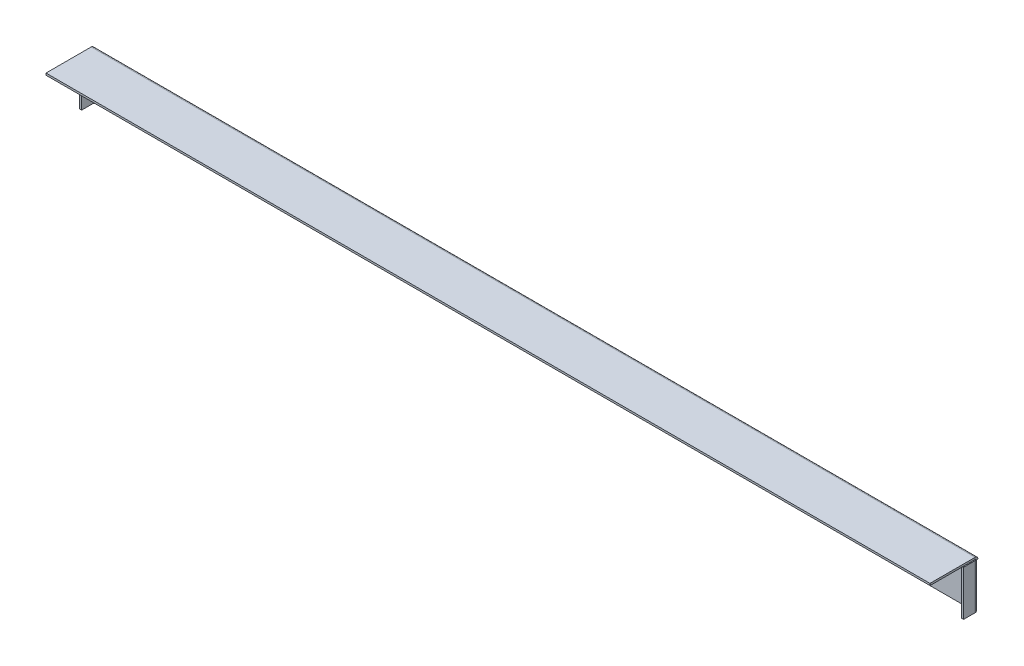
SolidWorks part; units mm, degrees
note: The reader was unsure of these and kept them because the rebuilt part matched: flange length of "Edge-Flange1", "Edge-Flange2".
ref_plane "Front Plane" through (0, 0, 0) normal (0, 0, 1) x (1, 0, 0)
ref_plane "Top Plane" through (0, 0, 0) normal (0, 1, 0) x (1, 0, 0)
ref_plane "Right Plane" through (0, 0, 0) normal (1, 0, 0) x (0, 0, -1)
sketch "BaseFlange" plane through (0, 0, 0) normal (0, 0, 1) x (1, 0, 0)
  line L1 (460, 0) -> (-460, 0)
  line L2 (460, 0) -> (460, -50)
  line L3 (460, -50) -> (-460, -50)
  line L4 (-460, 0) -> (-460, -50)
  line L5 (460, 0) -> (-460, -50) construction
  line L6 (460, -50) -> (-460, 0) construction
  point P0 (0, -25)
  dimension "BoxWidth" = 920
  dimension "D2" = 50
base flange "Base-Flange1" sketch "BaseFlange" thickness 2 reverse thickness direction yes parameters "D1"=1
edge flange "Edge-Flange1" sketch "Sketch8" flange angle 90 flange length 50 flange position material inside bend radius 1 thickness 2 parameters "D6"=10
sketch "Sketch8" plane through (0, 0, 2) normal (0, -1, 0) x (1, 0, 0)
  line L1 (-460, 0) -> (460, 0) construction
  line L2 (460, 0) -> (460, 48)
  line L3 (460, 48) -> (-460, 48)
  line L4 (-460, 48) -> (-460, 0)
  line L5 (-460, 0) -> (460, 0)
bend "EdgeBend1" bend radius 1 bend angle 90 parameters "D5"=1
edge flange "Edge-Flange2" sketch "Sketch13" flange profiles "Sketch13", "Sketch14" flange angle 90 flange length 15 flange position material inside bend radius 1 thickness 2 relief none parameters "D6"=10, "D8"=0.5
sketch "Sketch13" plane through (460, 0, 2) normal (-1, 0, 0) x (0, -1, 0)
  line L2 (3, 0) -> (3, 13)
  line L3 (3, 13) -> (50, 13)
  line L4 (50, 13) -> (50, 0)
  line L5 (50, 0) -> (3, 0) construction
  line L6 (50, 0) -> (3, 0)
sketch "Sketch14" plane through (-460, 0, 2) normal (1, 0, 0) x (0, 1, 0)
  line L0 (-3, 0) -> (-50, 0) construction
  line L1 (-3, 0) -> (-50, 0)
  line L2 (-3, 0) -> (-3, 13)
  line L3 (-3, 13) -> (-50, 13)
  line L4 (-50, 13) -> (-50, 0)
bend "EdgeBend2" bend radius 1 bend angle 90 parameters "D5"=2
bend "EdgeBend3" bend radius 1 bend angle 90 parameters "D5"=3
sketch "Bend-Lines1" [suppressed] plane through (0, 0, 0) normal (0, 1, 0) x (-1, 0, 0)
sketch "Bounding-Box1" [suppressed] plane through (0, 0, 0) normal (0, 1, 0) x (-1, 0, 0)
sheet metal parameters "Sheet-Metal1" thickness 2 parameters "D1"=1
flat pattern "Flat-Pattern1" [suppressed]
sketch "Bend-Lines2" plane through (0, 0, 0) normal (0, 1, 0) x (-1, 0, 0)
sketch3d "Bounding-Box2" [suppressed]
  line L0 (650, -25, 0) -> (-650, -25, 0) construction
  line L1 (650, 25, 0) -> (-650, 25, 0) construction
  line L2 (650, -25, 0) -> (650, 25, 0) construction
  line L3 (-650, -25, 0) -> (-650, 25, 0) construction
sheet metal parameters "Sheet-Metal2" thickness 2 parameters "D1"=1
flat pattern "Flat-Pattern1"
sketch "Bend-Lines2" plane through (0, 0, 0) normal (0, 0, -1) x (-1, 0, 0)
  line L0 (460, -1.7983) -> (-460, -1.7983) construction
  line L1 (460, -1.7983) -> (-460, -1.7983) construction
sketch3d "Bounding-Box2" [suppressed]
  line L0 (460, -50, 0) -> (-460, -50, 0) construction
  line L1 (460, 46.4033, 0) -> (-460, 46.4033, 0) construction
  line L2 (460, -50, 0) -> (460, 46.4033, 0) construction
  line L3 (-460, -50, 0) -> (-460, 46.4033, 0) construction
bend of the flat pattern "Flatten-<EdgeBend1>1"
sheet metal parameters "Sheet-Metal4" thickness 2 parameters "D1"=1
flat pattern "Flat-Pattern1"
sketch "Bend-Lines2" plane through (0, 0, 0) normal (0, 0, -1) x (-1, 0, 0)
  line L0 (460, -1.7983) -> (-460, -1.7983) construction
  line L1 (460, -1.7983) -> (-460, -1.7983) construction
  line L2 (458.2017, -50) -> (458.2017, -3) construction
  line L3 (-458.2017, -3) -> (-458.2017, -50) construction
  line L4 (458.2017, -50) -> (458.2017, -3) construction
  line L5 (-458.2017, -3) -> (-458.2017, -50) construction
sketch3d "Bounding-Box2" [suppressed]
  line L0 (471.4033, -50, 0) -> (-471.4033, -50, 0) construction
  line L1 (471.4033, 46.4033, 0) -> (-471.4033, 46.4033, 0) construction
  line L2 (471.4033, -50, 0) -> (471.4033, 46.4033, 0) construction
  line L3 (-471.4033, -50, 0) -> (-471.4033, 46.4033, 0) construction
bend of the flat pattern "Flatten-<EdgeBend1>1"
bend of the flat pattern "Flatten-<EdgeBend2>1"
bend of the flat pattern "Flatten-<EdgeBend3>1"
